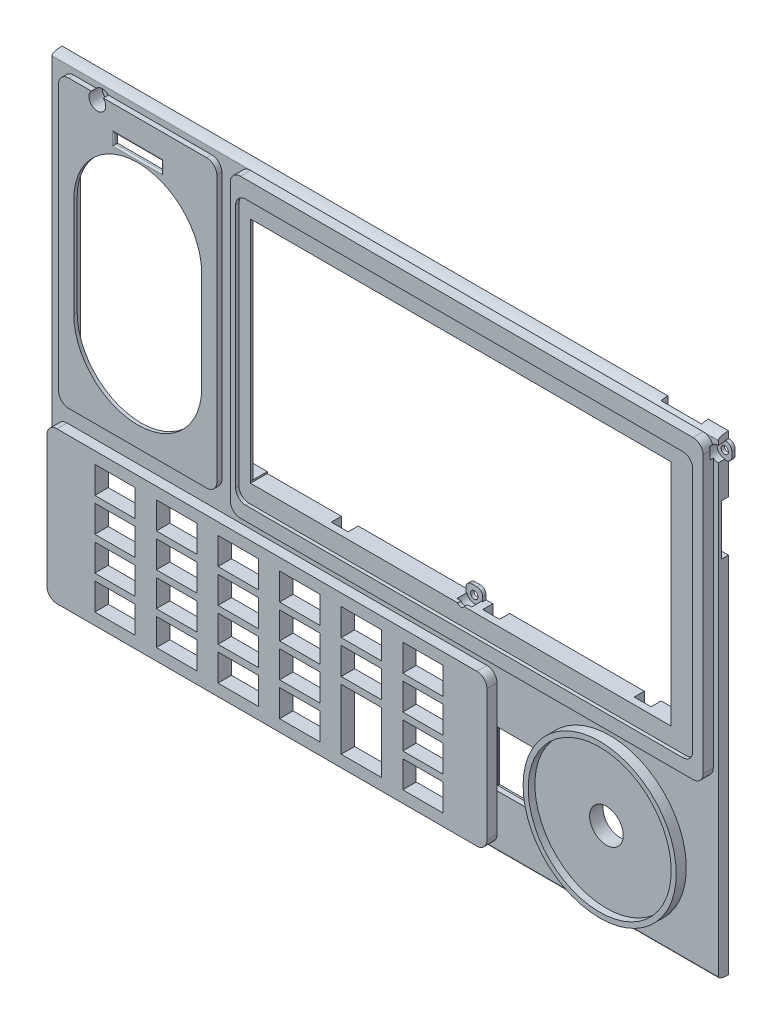
SolidWorks part; units mm, degrees
ref_plane "Front Plane" through (0, 0, 0) normal (0, 0, 1) x (1, 0, 0)
ref_plane "Top Plane" through (0, 0, 0) normal (0, 1, 0) x (1, 0, 0)
ref_plane "Right Plane" through (0, 0, 0) normal (1, 0, 0) x (0, 0, -1)
sketch "Sketch1" plane through (0, 0, 0) normal (0, 0, 1) x (1, 0, 0)
  line L1 (99, -70) -> (-99, -70)
  line L2 (99, -70) -> (99, 70)
  line L3 (99, 70) -> (-99, 70)
  line L4 (-99, -70) -> (-99, 70)
  line L5 (99, -70) -> (-99, 70) construction
  line L6 (99, 70) -> (-99, -70) construction
  point P0 (0, 0)
  dimension "D1" = 198
  dimension "D2" = 140
extrude "main_body" add sketch "Sketch1" along normal blind 3
fillet "long_corners" radius 3 2 edges at (0, 70, 3) (0, -70, 3) second distance 1 first distance on face at (0, 70, 1.5) first distance on face at (0, -70, 1.5)
sketch "Sketch2" plane through (0, 0, 3) normal (0, 0, 1) x (1, 0, 0)
  line L0 (-99, 24.75) -> (99, 24.75) construction
  line L1 (-99, 69) -> (-99, -69) construction
  line L2 (99, -69) -> (99, 69) construction
  line L3 (99, 69) -> (-99, 69) construction
  line L4 (-48.5, -17.75) -> (-95.5, -17.75)
  line L5 (-48.5, -17.75) -> (-48.5, 67.25)
  line L6 (-48.5, 67.25) -> (-95.5, 67.25)
  line L7 (-95.5, -17.75) -> (-95.5, 67.25)
  line L8 (-48.5, -17.75) -> (-95.5, 67.25) construction
  line L9 (-48.5, 67.25) -> (-95.5, -17.75) construction
  point P6 (-72, 24.75)
  dimension "D1" = 85
  dimension "D2" = 47
  dimension "D3" = 27
  dimension "D4" = 44.25
extrude "speaker" add sketch "Sketch2" along normal blind 1.5
fillet "speaker_corners" radius 3 4 edges at (-95.5, 67.25, 3.75) (-95.5, -17.75, 3.75) (-48.5, -17.75, 3.75) (-48.5, 67.25, 3.75)
sketch "Sketch19" plane through (0, 0, 4.5) normal (0, 0, 1) x (1, 0, 0)
  line L0 (-72, 67.25) -> (-72, -17.75) construction
  line L1 (-51.5, 67.25) -> (-92.5, 67.25) construction
  line L2 (-92.5, -17.75) -> (-51.5, -17.75) construction
  line L3 (-72, 7.25) -> (-72, 36.75) construction
  line L4 (-95.5, 64.25) -> (-95.5, -14.75) construction
  line L5 (-95.5, 24.75) -> (-48.5, 24.75) construction
  line L6 (-48.5, -14.75) -> (-48.5, 64.25) construction
  line L7 (-91, 7.25) -> (-91, 36.75)
  line L8 (-53, 7.25) -> (-53, 36.75)
  arc A0 (-91, 7.25) -> (-53, 7.25) centre (-72, 7.25) ccw
  arc A1 (-53, 36.75) -> (-91, 36.75) centre (-72, 36.75) ccw
  point P14 (-72, 22)
  point P19 (-72, -11.75)
  point P20 (-72, 55.75)
  dimension "D2" = 67.5
  dimension "D1" = 38
  dimension "D3" = 11.5
  dimension "D4" = 6
extrude "speaker_cut" cut sketch "Sketch19" against normal through all
sketch "Sketch21" plane through (0, 0, 0) normal (0, 0, -1) x (-1, 0, 0)
  line L0 (72, -11.75) -> (72, 55.75) construction
  line L2 (53, 7.25) -> (53, 36.75) construction
  line L3 (53, 22) -> (91, 22) construction
  line L4 (91, 36.75) -> (91, 7.25) construction
  line L5 (50.5, 61) -> (93.5, 61)
  line L6 (50.5, 61) -> (50.5, -17)
  line L7 (50.5, -17) -> (93.5, -17)
  line L8 (93.5, 61) -> (93.5, -17)
  line L9 (50.5, 61) -> (93.5, -17) construction
  line L10 (50.5, -17) -> (93.5, 61) construction
  arc A0 (53, 7.25) -> (91, 7.25) centre (72, 7.25) ccw construction
  arc A1 (91, 36.75) -> (53, 36.75) centre (72, 36.75) ccw construction
  point P14 (72, 22)
  dimension "D1" = 43
  dimension "D2" = 78
extrude "speaker_slot" cut sketch "Sketch21" against normal blind 3.5
sketch "Sketch3" plane through (0, 0, 3) normal (0, 0, 1) x (1, 0, 0)
  line L0 (-99, 25) -> (99, 25) construction
  line L1 (-99, 69) -> (-99, -69) construction
  line L2 (99, -69) -> (99, 69) construction
  line L4 (-48.5, -14.75) -> (-48.5, 64.25) construction
  line L5 (97.5, -19) -> (-43, -19)
  line L6 (97.5, -19) -> (97.5, 69)
  line L7 (97.5, 69) -> (-43, 69)
  line L8 (-43, -19) -> (-43, 69)
  line L9 (97.5, -19) -> (-43, 69) construction
  line L10 (97.5, 69) -> (-43, -19) construction
  line L11 (99, 70) -> (-99, 70) construction
  point P8 (27.25, 25)
  dimension "D1" = 1
  dimension "D2" = 88
  dimension "D3" = 140.5
  dimension "D4" = 1.5
  dimension "D5" = 5.5
extrude "lcd" add sketch "Sketch3" along normal blind 3
fillet "lcd_corners" radius 3 4 edges at (97.5, -19, 4.5) (-43, -19, 4.5)
sketch "Sketch9" plane through (0, 0, 6) normal (0, 0, 1) x (1, 0, 0)
  line L0 (-43, 24.5) -> (97.5, 24.5) construction
  line L1 (-43, 66) -> (-43, -16) construction
  line L2 (97.5, -16) -> (97.5, 66) construction
  line L3 (-40, -19) -> (94.5, -19) construction
  line L4 (94.4, -14.875) -> (-41.4, -14.875)
  line L5 (94.4, -14.875) -> (94.4, 63.875)
  line L6 (94.4, 63.875) -> (-41.4, 63.875)
  line L7 (-41.4, -14.875) -> (-41.4, 63.875)
  line L8 (94.4, -14.875) -> (-41.4, 63.875) construction
  line L9 (94.4, 63.875) -> (-41.4, -14.875) construction
  line L10 (94.5, 69) -> (-40, 69) construction
  line L11 (97.5, -16) -> (97.5, 66) construction
  point P6 (26.5, 24.5)
  dimension "D1" = 135.8
  dimension "D2" = 78.75
  dimension "D3" = 1.6
  dimension "D4" = 4.125
  dimension "D5" = 5.125
  dimension "D6" = 3.1
extrude "lcd_front" cut sketch "Sketch9" against normal blind 1
fillet "lcd_front_corners" radius 3 4 edges at (94.4, -14.875, 5.5) (94.4, 63.875, 5.5) (-41.4, 63.875, 5.5) (-41.4, -14.875, 5.5)
sketch "Sketch10" plane through (0, 0, 0) normal (0, 0, -1) x (-1, 0, 0)
  line L0 (-94.4, -11.875) -> (-94.4, 60.875) construction
  line L1 (-91.4, 63.875) -> (38.4, 63.875) construction
  line L2 (41.4, 63.875) -> (41.4, -14.875) construction
  line L3 (-94.4, 63.875) -> (41.4, 63.875) construction
  line L4 (38, -9.5) -> (-87, -9.5)
  line L5 (38, -9.5) -> (38, 58.5)
  line L6 (38, 58.5) -> (-87, 58.5)
  line L7 (-87, -9.5) -> (-87, 58.5)
  line L8 (-87, -9.5) -> (38, 58.5) construction
  line L9 (-87, 58.5) -> (38, -9.5) construction
  line L10 (-99, -70) -> (-99, 70) construction
  line L11 (-99, 70) -> (99, 70) construction
  line L13 (38.4, -14.875) -> (-91.4, -14.875) construction
  dimension "D1" = 125
  dimension "D2" = 68
  dimension "D3" = 12
  dimension "D4" = 3.4
  dimension "D5" = 11.5
  dimension "D6" = 5.375
  dimension "D7" = 7.4
  dimension "D8" = 5.375
  dimension "D9" = 5.375
extrude "lcd_back" cut sketch "Sketch10" against normal through all
sketch "Sketch56" plane through (0, 0, 0) normal (0, 0, -1) x (-1, 0, 0)
  line L0 (-87, -9.5) -> (38, -9.5) construction
  line L1 (-79, -9.5) -> (-74, -9.5)
  line L2 (-79, -9.5) -> (-79, -12.5)
  line L3 (-79, -12.5) -> (-74, -12.5)
  line L4 (-74, -9.5) -> (-74, -12.5)
  line L5 (38, 58.5) -> (-87, 58.5) construction
  line L6 (-34, -9.5) -> (-29, -9.5)
  line L7 (-34, -9.5) -> (-34, -12.5)
  line L8 (-34, -12.5) -> (-29, -12.5)
  line L9 (-29, -9.5) -> (-29, -12.5)
  line L10 (11, -9.5) -> (16, -9.5)
  line L11 (11, -9.5) -> (11, -12.5)
  line L12 (11, -12.5) -> (16, -12.5)
  line L13 (16, -9.5) -> (16, -12.5)
  line L14 (-79, 58.5) -> (-74, 58.5)
  line L15 (-79, 58.5) -> (-79, 61.5)
  line L16 (-79, 61.5) -> (-74, 61.5)
  line L17 (-74, 58.5) -> (-74, 61.5)
  line L18 (38, -9.5) -> (38, 58.5) construction
  line L19 (-34, 58.5) -> (-29, 58.5)
  line L20 (-34, 58.5) -> (-34, 61.5)
  line L21 (-34, 61.5) -> (-29, 61.5)
  line L22 (-29, 58.5) -> (-29, 61.5)
  line L23 (11, 58.5) -> (16, 58.5)
  line L24 (11, 58.5) -> (11, 61.5)
  line L25 (11, 61.5) -> (16, 61.5)
  line L26 (16, 58.5) -> (16, 61.5)
  line L27 (38, 58) -> (42, 58)
  line L28 (38, 58) -> (38, -9)
  line L29 (38, -9) -> (42, -9)
  line L30 (42, 58) -> (42, -9)
  line L31 (-99, -70) -> (-99, 70) construction
  line L32 (-99, 70) -> (99, 70) construction
  point P34 (-29, -11)
  dimension "D1" = 5
  dimension "D2" = 5
  dimension "D3" = 5
  dimension "D4" = 5
  dimension "D5" = 5
  dimension "D6" = 5
  dimension "D7" = 67
  dimension "D8" = 4
  dimension "D9" = 3
  dimension "D10" = 3
  dimension "D11" = 3
  dimension "D12" = 3
  dimension "D13" = 3
  dimension "D14" = 3
  dimension "D15" = 40
  dimension "D16" = 40
  dimension "D17" = 20
  dimension "D18" = 20
  dimension "D19" = 40
  dimension "D20" = 40
  dimension "D21" = 12
extrude "lcd_glue_points" cut sketch "Sketch56" against normal blind 3
sketch "Sketch4" plane through (0, 0, 3) normal (0, 0, 1) x (1, 0, 0)
  line L0 (-99, -45.75) -> (99, -45.75) construction
  line L1 (-99, 69) -> (-99, -69) construction
  line L2 (99, -69) -> (99, 69) construction
  line L4 (-92.5, -17.75) -> (-51.5, -17.75) construction
  line L5 (33.25, -68.25) -> (-97.5, -68.25)
  line L6 (33.25, -68.25) -> (33.25, -23.25)
  line L7 (33.25, -23.25) -> (-97.5, -23.25)
  line L8 (-97.5, -68.25) -> (-97.5, -23.25)
  line L9 (33.25, -68.25) -> (-97.5, -23.25) construction
  line L10 (33.25, -23.25) -> (-97.5, -68.25) construction
  line L11 (-99, -70) -> (99, -70) construction
  point P8 (-32.125, -45.75)
  dimension "D1" = 1.75
  dimension "D2" = 130.75
  dimension "D3" = 45
  dimension "D4" = 1.5
  dimension "D5" = 5.5
extrude "keypad" add sketch "Sketch4" along normal blind 3
fillet "keypad_corners" radius 3 4 edges at (-97.5, -68.25, 4.5) (33.25, -68.25, 4.5) (33.25, -23.25, 4.5) (-97.5, -23.25, 4.5)
sketch "Sketch25" plane through (0, 0, 6) normal (0, 0, 1) x (1, 0, 0)
  line L0 (-97.5, -30.75) -> (33.25, -30.75) construction
  line L1 (30.25, -23.25) -> (-94.5, -23.25) construction
  line L2 (-94.5, -68.25) -> (30.25, -68.25) construction
  line L3 (-77.25, -23.25) -> (-77.25, -68.25) construction
  line L5 (-34.65, -64.75) -> (33.25, -64.75) construction
  line L6 (-97.5, -26.25) -> (-97.5, -65.25) construction
  line L11 (33.25, -65.25) -> (33.25, -26.25) construction
  line L12 (-58.95, -23.25) -> (-58.95, -68.25) construction
  line L13 (-97.5, -40.75) -> (33.25, -40.75) construction
  line L14 (30.25, -23.25) -> (-94.5, -23.25) construction
  line L15 (-40.65, -23.25) -> (-40.65, -68.25) construction
  line L16 (-94.5, -68.25) -> (30.25, -68.25) construction
  line L17 (-71.25, -34.75) -> (-83.25, -34.75)
  line L18 (-22.35, -23.25) -> (-22.35, -68.25) construction
  line L19 (-97.5, -50.75) -> (33.25, -50.75) construction
  line L20 (-4.05, -23.25) -> (-4.05, -68.25) construction
  line L21 (-71.25, -34.75) -> (-71.25, -26.75)
  line L22 (14.25, -23.25) -> (14.25, -68.25) construction
  line L23 (-97.5, -26.25) -> (-97.5, -65.25) construction
  line L24 (-97.5, -60.75) -> (33.25, -60.75) construction
  line L25 (-71.25, -26.75) -> (-83.25, -26.75)
  line L26 (-83.25, -34.75) -> (-83.25, -26.75)
  line L27 (-71.25, -34.75) -> (-83.25, -26.75) construction
  line L28 (-71.25, -26.75) -> (-83.25, -34.75) construction
  line L29 (-71.25, -44.75) -> (-83.25, -44.75)
  line L30 (-71.25, -44.75) -> (-71.25, -36.75)
  line L31 (-71.25, -36.75) -> (-83.25, -36.75)
  line L32 (-83.25, -44.75) -> (-83.25, -36.75)
  line L33 (-71.25, -44.75) -> (-83.25, -36.75) construction
  line L34 (-71.25, -36.75) -> (-83.25, -44.75) construction
  line L35 (-71.25, -54.75) -> (-83.25, -54.75)
  line L36 (-71.25, -54.75) -> (-71.25, -46.75)
  line L37 (-71.25, -46.75) -> (-83.25, -46.75)
  line L38 (-83.25, -54.75) -> (-83.25, -46.75)
  line L39 (-71.25, -54.75) -> (-83.25, -46.75) construction
  line L40 (-71.25, -46.75) -> (-83.25, -54.75) construction
  line L41 (-71.25, -64.75) -> (-83.25, -64.75)
  line L42 (-71.25, -64.75) -> (-71.25, -56.75)
  line L43 (-71.25, -56.75) -> (-83.25, -56.75)
  line L44 (-83.25, -64.75) -> (-83.25, -56.75)
  line L45 (-71.25, -64.75) -> (-83.25, -56.75) construction
  line L46 (-71.25, -56.75) -> (-83.25, -64.75) construction
  line L47 (-52.95, -34.75) -> (-64.95, -34.75)
  line L48 (-52.95, -34.75) -> (-52.95, -26.75)
  line L49 (-52.95, -26.75) -> (-64.95, -26.75)
  line L50 (-64.95, -34.75) -> (-64.95, -26.75)
  line L51 (-52.95, -34.75) -> (-64.95, -26.75) construction
  line L52 (-52.95, -26.75) -> (-64.95, -34.75) construction
  line L53 (-52.95, -44.75) -> (-64.95, -44.75)
  line L54 (-52.95, -44.75) -> (-52.95, -36.75)
  line L55 (-52.95, -36.75) -> (-64.95, -36.75)
  line L56 (-64.95, -44.75) -> (-64.95, -36.75)
  line L57 (-52.95, -44.75) -> (-64.95, -36.75) construction
  line L58 (-52.95, -36.75) -> (-64.95, -44.75) construction
  line L59 (-52.95, -54.75) -> (-64.95, -54.75)
  line L60 (-52.95, -54.75) -> (-52.95, -46.75)
  line L61 (-52.95, -46.75) -> (-64.95, -46.75)
  line L62 (-64.95, -54.75) -> (-64.95, -46.75)
  line L63 (-52.95, -54.75) -> (-64.95, -46.75) construction
  line L64 (-52.95, -46.75) -> (-64.95, -54.75) construction
  line L65 (-52.95, -64.75) -> (-64.95, -64.75)
  line L66 (-52.95, -64.75) -> (-52.95, -56.75)
  line L67 (-52.95, -56.75) -> (-64.95, -56.75)
  line L68 (-64.95, -64.75) -> (-64.95, -56.75)
  line L69 (-52.95, -64.75) -> (-64.95, -56.75) construction
  line L70 (-52.95, -56.75) -> (-64.95, -64.75) construction
  line L71 (-34.65, -34.75) -> (-46.65, -34.75)
  line L72 (-34.65, -34.75) -> (-34.65, -26.75)
  line L73 (-34.65, -26.75) -> (-46.65, -26.75)
  line L74 (-46.65, -34.75) -> (-46.65, -26.75)
  line L75 (-34.65, -34.75) -> (-46.65, -26.75) construction
  line L76 (-34.65, -26.75) -> (-46.65, -34.75) construction
  line L77 (-34.65, -44.75) -> (-46.65, -44.75)
  line L78 (-34.65, -44.75) -> (-34.65, -36.75)
  line L79 (-34.65, -36.75) -> (-46.65, -36.75)
  line L80 (-46.65, -44.75) -> (-46.65, -36.75)
  line L81 (-34.65, -44.75) -> (-46.65, -36.75) construction
  line L82 (-34.65, -36.75) -> (-46.65, -44.75) construction
  line L83 (-34.65, -54.75) -> (-46.65, -54.75)
  line L84 (-34.65, -54.75) -> (-34.65, -46.75)
  line L85 (-34.65, -46.75) -> (-46.65, -46.75)
  line L86 (-46.65, -54.75) -> (-46.65, -46.75)
  line L87 (-34.65, -54.75) -> (-46.65, -46.75) construction
  line L88 (-34.65, -46.75) -> (-46.65, -54.75) construction
  line L89 (-34.65, -64.75) -> (-46.65, -64.75)
  line L90 (-34.65, -64.75) -> (-34.65, -56.75)
  line L91 (-34.65, -56.75) -> (-46.65, -56.75)
  line L92 (-46.65, -64.75) -> (-46.65, -56.75)
  line L93 (-34.65, -64.75) -> (-46.65, -56.75) construction
  line L94 (-34.65, -56.75) -> (-46.65, -64.75) construction
  line L95 (-16.35, -34.75) -> (-28.35, -34.75)
  line L96 (-16.35, -34.75) -> (-16.35, -26.75)
  line L97 (-16.35, -26.75) -> (-28.35, -26.75)
  line L98 (-28.35, -34.75) -> (-28.35, -26.75)
  line L99 (-16.35, -34.75) -> (-28.35, -26.75) construction
  line L100 (-16.35, -26.75) -> (-28.35, -34.75) construction
  line L101 (-16.35, -44.75) -> (-28.35, -44.75)
  line L102 (-16.35, -44.75) -> (-16.35, -36.75)
  line L103 (-16.35, -36.75) -> (-28.35, -36.75)
  line L104 (-28.35, -44.75) -> (-28.35, -36.75)
  line L105 (-16.35, -44.75) -> (-28.35, -36.75) construction
  line L106 (-16.35, -36.75) -> (-28.35, -44.75) construction
  line L111 (-16.35, -54.75) -> (-28.35, -54.75)
  line L112 (-16.35, -54.75) -> (-16.35, -46.75)
  line L113 (-16.35, -46.75) -> (-28.35, -46.75)
  line L114 (-28.35, -54.75) -> (-28.35, -46.75)
  line L115 (-16.35, -54.75) -> (-28.35, -46.75) construction
  line L116 (-16.35, -46.75) -> (-28.35, -54.75) construction
  line L117 (-16.35, -64.75) -> (-28.35, -64.75)
  line L118 (-16.35, -64.75) -> (-16.35, -56.75)
  line L119 (-16.35, -56.75) -> (-28.35, -56.75)
  line L120 (-28.35, -64.75) -> (-28.35, -56.75)
  line L121 (-16.35, -64.75) -> (-28.35, -56.75) construction
  line L122 (-16.35, -56.75) -> (-28.35, -64.75) construction
  line L127 (1.95, -34.75) -> (-10.05, -34.75)
  line L128 (1.95, -34.75) -> (1.95, -26.75)
  line L129 (1.95, -26.75) -> (-10.05, -26.75)
  line L130 (-10.05, -34.75) -> (-10.05, -26.75)
  line L131 (1.95, -34.75) -> (-10.05, -26.75) construction
  line L132 (1.95, -26.75) -> (-10.05, -34.75) construction
  line L133 (20.25, -34.75) -> (8.25, -34.75)
  line L134 (20.25, -34.75) -> (20.25, -26.75)
  line L135 (20.25, -26.75) -> (8.25, -26.75)
  line L136 (8.25, -34.75) -> (8.25, -26.75)
  line L137 (20.25, -34.75) -> (8.25, -26.75) construction
  line L138 (20.25, -26.75) -> (8.25, -34.75) construction
  line L139 (1.95, -44.75) -> (-10.05, -44.75)
  line L140 (1.95, -44.75) -> (1.95, -36.75)
  line L141 (1.95, -36.75) -> (-10.05, -36.75)
  line L142 (-10.05, -44.75) -> (-10.05, -36.75)
  line L143 (1.95, -44.75) -> (-10.05, -36.75) construction
  line L144 (1.95, -36.75) -> (-10.05, -44.75) construction
  line L145 (20.25, -44.75) -> (8.25, -44.75)
  line L146 (20.25, -44.75) -> (20.25, -36.75)
  line L147 (20.25, -36.75) -> (8.25, -36.75)
  line L148 (8.25, -44.75) -> (8.25, -36.75)
  line L149 (20.25, -44.75) -> (8.25, -36.75) construction
  line L150 (20.25, -36.75) -> (8.25, -44.75) construction
  line L151 (20.25, -54.75) -> (8.25, -54.75)
  line L152 (20.25, -54.75) -> (20.25, -46.75)
  line L153 (20.25, -46.75) -> (8.25, -46.75)
  line L154 (8.25, -54.75) -> (8.25, -46.75)
  line L155 (20.25, -54.75) -> (8.25, -46.75) construction
  line L156 (20.25, -46.75) -> (8.25, -54.75) construction
  line L157 (20.25, -64.75) -> (8.25, -64.75)
  line L158 (20.25, -64.75) -> (20.25, -56.75)
  line L159 (20.25, -56.75) -> (8.25, -56.75)
  line L160 (8.25, -64.75) -> (8.25, -56.75)
  line L161 (20.25, -64.75) -> (8.25, -56.75) construction
  line L162 (20.25, -56.75) -> (8.25, -64.75) construction
  line L163 (1.95, -64.75) -> (-10.05, -64.75)
  line L164 (1.95, -64.75) -> (1.95, -46.75)
  line L165 (1.95, -46.75) -> (-10.05, -46.75)
  line L166 (-10.05, -64.75) -> (-10.05, -46.75)
  line L167 (1.95, -64.75) -> (-10.05, -46.75) construction
  line L168 (1.95, -46.75) -> (-10.05, -64.75) construction
  point P34 (-77.25, -30.75)
  point P39 (-77.25, -40.75)
  point P44 (-77.25, -50.75)
  point P49 (-77.25, -60.75)
  point P54 (-58.95, -30.75)
  point P59 (-58.95, -40.75)
  point P64 (-58.95, -50.75)
  point P69 (-58.95, -60.75)
  point P74 (-40.65, -30.75)
  point P79 (-40.65, -40.75)
  point P84 (-40.65, -50.75)
  point P89 (-40.65, -60.75)
  point P94 (-22.35, -30.75)
  point P99 (-22.35, -40.75)
  point P104 (-22.35, -50.75)
  point P109 (-22.35, -60.75)
  point P114 (-4.05, -30.75)
  point P119 (14.25, -30.75)
  point P124 (-4.05, -40.75)
  point P129 (14.25, -40.75)
  point P134 (14.25, -50.75)
  point P139 (14.25, -60.75)
  point P144 (-4.05, -55.75)
  dimension "D1" = 19
  dimension "D2" = 18.3
  dimension "D3" = 18.3
  dimension "D4" = 18.3
  dimension "D5" = 18.3
  dimension "D6" = 18.3
  dimension "D7" = 20.25
  dimension "D8" = 7.5
  dimension "D9" = 10
  dimension "D10" = 10
  dimension "D11" = 10
  dimension "D12" = 7.5
  dimension "D13" = 12
  dimension "D14" = 12
  dimension "D15" = 12
  dimension "D16" = 12
  dimension "D17" = 12
  dimension "D18" = 12
  dimension "D19" = 12
  dimension "D20" = 12
  dimension "D21" = 12
  dimension "D22" = 12
  dimension "D23" = 12
  dimension "D24" = 12
  dimension "D25" = 12
  dimension "D26" = 12
  dimension "D27" = 12
  dimension "D28" = 12
  dimension "D29" = 12
  dimension "D30" = 12
  dimension "D31" = 12
  dimension "D32" = 12
  dimension "D33" = 12
  dimension "D34" = 12
  dimension "D35" = 12
  dimension "D36" = 8
  dimension "D37" = 8
  dimension "D38" = 8
  dimension "D39" = 8
  dimension "D40" = 8
  dimension "D41" = 8
  dimension "D42" = 18
  dimension "D43" = 8
  dimension "D44" = 8
  dimension "D45" = 8
  dimension "D46" = 8
  dimension "D47" = 8
  dimension "D48" = 8
  dimension "D49" = 8
  dimension "D50" = 8
  dimension "D51" = 8
  dimension "D52" = 8
  dimension "D53" = 8
  dimension "D54" = 8
  dimension "D55" = 8
  dimension "D56" = 8
  dimension "D57" = 8
  dimension "D58" = 8
  dimension "D59" = 5
extrude "keypad_cuts_0.8" cut sketch "Sketch25" against normal through all
sketch "Sketch5" plane through (0, 0, 3) normal (0, 0, 1) x (1, 0, 0)
  line L0 (33.25, -45.75) -> (99, -45.75) construction
  line L1 (33.25, -65.25) -> (33.25, -26.25) construction
  line L2 (99, -69) -> (99, 69) construction
  circle A0 centre (66.75, -45.75) radius 22.75
  dimension "D1" = 45.5
  dimension "D2" = 32.25
  dimension "D3" = 33.5
extrude "vfo" add sketch "Sketch5" along normal blind 3
sketch "Sketch7" plane through (0, 0, 6) normal (0, 0, 1) x (1, 0, 0)
  line L0 (44, -45.75) -> (89.5, -45.75) construction
  line L1 (66.75, -23) -> (66.75, -68.5) construction
  circle A0 centre (66.75, -45.75) radius 22.75 construction
  circle A1 centre (66.75, -45.75) radius 22.75 construction
  circle A2 centre (66.75, -45.75) radius 5
  dimension "D1" = 10
extrude "vfo_encoder_knob_cut" cut sketch "Sketch7" against normal through all
sketch "esp32" plane through (0, 0, 0) normal (0, 0, -1) x (-1, 0, 0)
  line L0 (99, -70) -> (-99, -70) construction
  line L1 (-50.5, -37.5) -> (-32, -37.5)
  line L2 (-50.5, -37.5) -> (-50.5, -54)
  line L3 (-50.5, -54) -> (-32, -54)
  line L4 (-32, -37.5) -> (-32, -54)
  line L5 (-99, -70) -> (-99, 70) construction
  dimension "D1" = 16
  dimension "D2" = 48.5
  dimension "D3" = 16.5
  dimension "D4" = 18.5
extrude "esp32_can_cut" cut sketch "esp32" against normal blind 3
sketch "Sketch47" plane through (0, 0, 0) normal (0, 0, -1) x (-1, 0, 0)
  line L0 (-50.5, -54) -> (-32, -54) construction
  line L1 (-31, -55) -> (-58, -55)
  line L2 (-31, -55) -> (-31, -36.5)
  line L3 (-31, -36.5) -> (-58, -36.5)
  line L4 (-58, -55) -> (-58, -36.5)
  line L5 (-31, -55) -> (-58, -36.5) construction
  line L6 (-31, -36.5) -> (-58, -55) construction
  line L7 (-50.5, -37.5) -> (-50.5, -54) construction
  point P0 (-44.5, -45.75)
  dimension "D1" = 27
  dimension "D2" = 18.5
  dimension "D3" = 1
  dimension "D4" = 7.5
extrude "esp32_ex_cut" cut sketch "Sketch47" against normal blind 1.5
sketch "Sketch49" plane through (0, 0, 0) normal (0, 0, -1) x (-1, 0, 0)
  line L0 (72, 58.25) -> (72, 67.25) construction
  line L3 (51.5, 67.25) -> (92.5, 67.25) construction
  line L4 (79, 56.75) -> (65, 56.75)
  line L5 (79, 56.75) -> (79, 59.75)
  line L6 (79, 59.75) -> (65, 59.75)
  line L7 (65, 56.75) -> (65, 59.75)
  line L8 (79, 56.75) -> (65, 59.75) construction
  line L9 (79, 59.75) -> (65, 56.75) construction
  point P6 (72, 58.25)
  dimension "D1" = 14
  dimension "D2" = 3
  dimension "D3" = 9
extrude "amb_sensor" cut sketch "Sketch49" against normal through all
fillet "amb_corners" radius 0.5 4 edges at (-65, 58.25, 4.5) (-72, 59.75, 4.5) (-79, 58.25, 4.5) (-72, 56.75, 4.5)
sketch "Sketch55" plane through (0, 0, 0) normal (0, 0, -1) x (-1, 0, 0)
  line L0 (-99, -70) -> (-99, 70) construction
  line L5 (-93, 70) -> (-81, 70)
  line L6 (-93, 70) -> (-93, 58.5)
  line L11 (-93, 58.5) -> (-81, 58.5)
  line L12 (-81, 70) -> (-81, 58.5)
  line L13 (94.5, 48) -> (99, 48)
  line L14 (94.5, 48) -> (94.5, 33)
  line L15 (94.5, 33) -> (99, 33)
  line L16 (99, 48) -> (99, 33)
  line L17 (94.5, 48) -> (99, 33) construction
  line L18 (94.5, 33) -> (99, 48) construction
  line L23 (99, 65.5) -> (-99, 65.5) construction
  line L24 (99, -8.5) -> (-99, -8.5) construction
  line L35 (-99, -68) -> (99, -68) construction
  line L36 (99, -70) -> (-99, -70) construction
  line L42 (-99, 53) -> (-93, 53)
  line L43 (-99, 53) -> (-99, 38)
  line L44 (-99, 70) -> (99, 70) construction
  line L45 (-99, 38) -> (-93, 38)
  line L46 (99, 70) -> (99, -70) construction
  line L47 (-93, 53) -> (-93, 38)
  circle A1 centre (49.5, 65.5) radius 3
  circle A2 centre (-24.5, 65.5) radius 3
  circle A4 centre (49.5, -8.5) radius 3
  circle A6 centre (-68, -68) radius 3
  circle A7 centre (-1, -68) radius 3
  circle A9 centre (-32, 65.5) radius 3
  point P10 (96.75, 40.5)
  dimension "D8" = 6
  dimension "D9" = 6
  dimension "D13" = 6
  dimension "D18" = 2
  dimension "D19" = 6
  dimension "D21" = 6
  dimension "D22" = 6
  dimension "D1" = 12
  dimension "D3" = 11.5
  dimension "D4" = 0
  dimension "D5" = 6
  dimension "D6" = 4.5
  dimension "D11" = 49.5
  dimension "D12" = 123.5
  dimension "D14" = 7.5
  dimension "D15" = 61.5
  dimension "D24" = 100
  dimension "D25" = 15
  dimension "D26" = 4.5
  dimension "D27" = 0
  dimension "D28" = 22
  dimension "D29" = 49.5
  dimension "D30" = 67
  dimension "D31" = 6
  dimension "D32" = 15
  dimension "D33" = 0
  dimension "D34" = 17
extrude "conn_cutouts" cut sketch "Sketch55" against normal blind 2
fillet "Fillet1" radius 2 1 edges at (-38, 24.5, 3)
fillet "Fillet2" radius 5 1 edges at (-42, 24.5, 0)
sketch "Sketch57" plane through (0, 0, 0) normal (0, 0, -1) x (-1, 0, 0)
  line L0 (99, 70) -> (99, 48) construction
  line L1 (-24, -22) -> (89, -22)
  line L2 (-24, -22) -> (-24, -67.5)
  line L3 (-24, -67.5) -> (89, -67.5)
  line L4 (89, -22) -> (89, -67.5)
  line L5 (99, -70) -> (1.2361, -70) construction
  dimension "D1" = 113
  dimension "D2" = 45.5
  dimension "D3" = 10
  dimension "D4" = 2.5
extrude "keyboard_back" cut sketch "Sketch57" against normal blind 2
sketch "Sketch58" plane through (0, -9.5, 0) normal (0, 1, 0) x (1, 0, 0)
  line L1 (27, -1) -> (22, -1)
  line L2 (27, -1) -> (27, 0)
  line L3 (27, 0) -> (22, 0)
  line L4 (22, -1) -> (22, 0)
  line L5 (27, -1) -> (22, 0) construction
  line L6 (27, 0) -> (22, -1) construction
  line L7 (29, -3) -> (29, 0) construction
  line L9 (29, 0) -> (-11, 0) construction
  point P0 (24.5, -0.5)
  dimension "D1" = 1
  dimension "D2" = 5
  dimension "D3" = 2
  dimension "D4" = 0
extrude "behind_lcd_screew_mount" add sketch "Sketch58" along normal blind 3
sketch "Sketch59" plane through (-99, 0, 0) normal (-1, 0, 0) x (0, 0, 1)
  line L0 (0, 70) -> (0, 48) construction
  line L1 (0, -66.5) -> (1, -66.5)
  line L2 (0, -66.5) -> (0, -69.5)
  line L3 (0, -69.5) -> (1, -69.5)
  line L4 (1, -66.5) -> (1, -69.5)
  dimension "D1" = 1
  dimension "D2" = 3
  dimension "D3" = 66.5
extrude "keyb_screw_mount" add sketch "Sketch59" along normal blind 1
sketch "Sketch60" plane through (99, 0, 0) normal (1, 0, 0) x (0, 0, -1)
  line L0 (0, -70) -> (0, 38) construction
  line L1 (0, 68) -> (-1, 68)
  line L2 (0, 68) -> (0, 63)
  line L3 (0, 63) -> (-1, 63)
  line L4 (-1, 68) -> (-1, 63)
  dimension "D1" = 63
  dimension "D2" = 5
  dimension "D3" = 1
extrude "right_corner_screw_mount" add sketch "Sketch60" along normal blind 2
sketch "Sketch61" plane through (0, 0, 0) normal (0, 0, -1) x (-1, 0, 0)
  line L0 (-99, 70) -> (-93, 70) construction
  line L1 (-99, 68) -> (-99, 70) construction
  line L2 (-99, -9) -> (99, -9) construction
  line L3 (99, 70) -> (99, 48) construction
  line L5 (-99, -70) -> (-99, 38) construction
  line L6 (99, 70) -> (99, 48) construction
  line L7 (-3.2361, -70) -> (-65.7639, -70) construction
  line L8 (99, -69.5) -> (99, -70) construction
  line L9 (99, -70) -> (1.2361, -70) construction
  line L10 (-81, 70) -> (99, 70) construction
  circle A0 centre (-98.9, 65.5) radius 1.1
  circle A1 centre (-24.5, -9) radius 1.1
  circle A2 centre (98, -68) radius 1.1
  circle A3 centre (84, 65.5) radius 1.1
  dimension "D1" = 2.2
  dimension "D6" = 2.2
  dimension "D9" = 2.2
  dimension "D10" = 2.2
  dimension "D2" = 4.5
  dimension "D3" = 0.1
  dimension "D4" = 61
  dimension "D5" = 123.5
  dimension "D7" = 1
  dimension "D8" = 2
  dimension "D11" = 15
  dimension "D12" = 4.5
extrude "ui_screws" cut sketch "Sketch61" against normal through all
sketch "Sketch62" plane through (0, 0, 6) normal (0, 0, 1) x (1, 0, 0)
  line L0 (97.8, 65.5) -> (100, 65.5) construction
  line L1 (-98, -66.9) -> (-98, -69.1) construction
  line L2 (98.9, 66.6) -> (98.9, 64.4) construction
  line L4 (-96.9, -68) -> (-99.1, -68) construction
  circle A0 centre (24.5, -9) radius 2.25
  arc A1 (99, 66.5954) -> (99, 64.4046) centre (98.9, 65.5) ccw construction
  arc A2 (99, 64.4046) -> (99, 66.5954) centre (98.9, 65.5) ccw construction
  circle A3 centre (98.9, 65.5) radius 2.25
  arc A4 (-97.5417, -69) -> (-99, -67.5417) centre (-98, -68) ccw construction
  arc A5 (-98.4583, -69) -> (-97.5417, -69) centre (-98, -68) ccw construction
  arc A6 (-99, -67.5417) -> (-99, -68.4583) centre (-98, -68) ccw construction
  circle A7 centre (-98, -68) radius 2.25
  dimension "D1" = 4.5
  dimension "D2" = 4.5
  dimension "D3" = 4.5
extrude "ui_screw_head" cut sketch "Sketch62" against normal blind 3 from offset 2 offset against normal yes
fillet "ui_screw_mount_corners" radius 1.75 6 edges at (-100, -66.5, 0.5) (-100, -69.5, 0.5) (101, 63, 0.5) (101, 68, 0.5) (22, -6.5, 0.5) (27, -6.5, 0.5)
sketch "Sketch63" plane through (0, 0, 6) normal (0, 0, 1) x (1, 0, 0)
  circle A0 centre (66.75, -45.75) radius 21.25
  dimension "D1" = 42.5
extrude "enc_knob_slot" cut sketch "Sketch63" against normal blind 2
sketch "Sketch64" plane through (0, 0, 4.5) normal (0, 0, 1) x (1, 0, 0)
  circle A0 centre (-84, 65.5) radius 2.5
  dimension "D1" = 5
extrude "on_speaker_ui_screw_head" cut sketch "Sketch64" against normal blind 4
